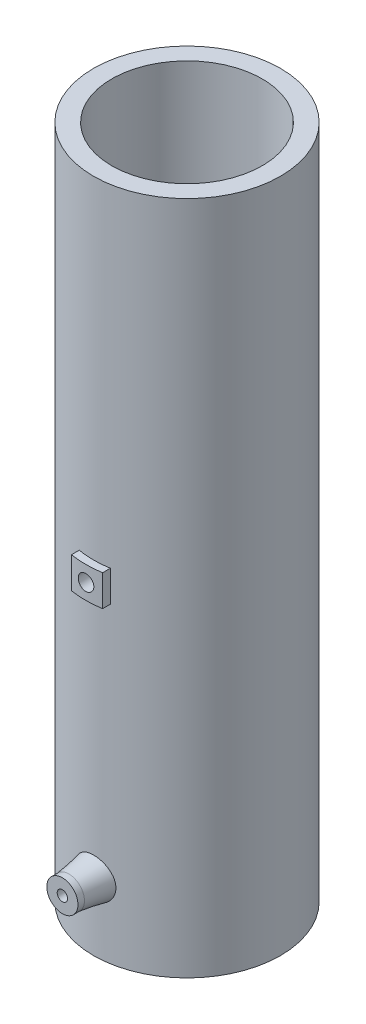
SolidWorks part; units mm, degrees
ref_plane "Front Plane" through (0, 0, 0) normal (0, 0, 1) x (1, 0, 0)
ref_plane "Top Plane" through (0, 0, 0) normal (0, 1, 0) x (1, 0, 0)
ref_plane "Right Plane" through (0, 0, 0) normal (1, 0, 0) x (0, 0, -1)
sketch "Sketch1" plane through (0, 0, 0) normal (0, 1, 0) x (1, 0, 0)
  circle A0 centre (0, 0) radius 18
  circle A1 centre (0, 0) radius 14.5
  dimension "D1" = 36
  dimension "D2" = 29
extrude "Boss-Extrude1" add sketch "Sketch1" along normal blind 130
fillet "Fillet1" radius 3 1 edges at (0, 0, 14.5)
ref_plane "Plane1" through (0, 0, 18) normal (0, 0, 1) x (1, 0, 0)
ref_plane "Plane2" through (0, 60, 0) normal (0, 1, 0) x (1, 0, 0)
sketch "Sketch3" plane through (0, 60, 0) normal (0, 1, 0) x (1, 0, 0)
  line L0 (-3, -19.2678) -> (-3, -17.7482)
  line L1 (-19.8, 0) -> (19.8, 0) construction
  line L2 (3, -19.2678) -> (3, -17.7482)
  line L3 (3, 19.2678) -> (3, 17.7482)
  line L4 (-3, 19.2678) -> (-3, 17.7482)
  arc A0 (-3, -17.7482) -> (3, -17.7482) centre (0, 0) ccw
  arc A1 (-3, -19.2678) -> (3, -19.2678) centre (0, 0) ccw
  arc A2 (-3, 19.2678) -> (3, 19.2678) centre (0, 0) cw
  arc A3 (-3, 17.7482) -> (3, 17.7482) centre (0, 0) cw
  dimension "D1" = 36
  dimension "D2" = 39
  dimension "D3" = 3
  dimension "D4" = 3
  dimension "D5" = 19.2678
extrude "Boss-Extrude2" add sketch "Sketch3" along normal blind 6
sketch "Sketch4" plane through (0, 0, 18) normal (0, 0, 1) x (1, 0, 0)
  line L0 (-3, 66) -> (-3, 60) construction
  line L1 (3, 66) -> (-3, 66) construction
  circle A0 centre (0, 63) radius 1.5
  dimension "D1" = 3
  dimension "D2" = 3
  dimension "D3" = 3
extrude "Cut-Extrude1" cut sketch "Sketch4" along normal blind 1.5 and the other way blind 1.5 contours A0
mirror "Mirror1" about plane through (0, 0, 0) normal (0, 0, 1) of "Cut-Extrude1"
sketch "Sketch5" plane through (0, 0, 18) normal (0, 0, 1) x (1, 0, 0)
  circle A0 centre (0, 13) radius 3
  circle A1 centre (0, 63) radius 1.5 construction
  dimension "D1" = 6
  dimension "D2" = 50
extrude "Boss-Extrude3" add sketch "Sketch5" along normal blind 6 and the other way blind 1 separate body
sketch "Sketch6" plane through (0, 0, 0) normal (1, 0, 0) x (0, 0, -1)
  line L0 (-11, 13) -> (-11, 19) construction
  line L1 (-24, 16) -> (-24, 10) construction
  line L2 (-17, 16) -> (-24, 16) construction
  line L3 (-22.7446, 16) -> (-22.7446, 13)
  line L4 (-22.7446, 13) -> (-16.5007, 13)
  line L5 (-16.5007, 17.1546) -> (-16.5007, 13)
  spline S0 degree 3 poles (-16.5007, 17.1546) (-18.5486, 16.6168) (-20.6299, 16.2319) (-22.7446, 16) knots 0.476119 0.476119 0.476119 0.476119 1 1 1 1
  dimension "D4" = 3
  dimension "D1" = 13
  dimension "D2" = 13
  dimension "D3" = 3
revolve "Revolve1" add sketch "Sketch6" angle 360 about L4
sketch "Sketch7" plane through (0, 0, 24) normal (0, 0, 1) x (1, 0, 0)
  circle A0 centre (0, 13) radius 1
  dimension "D1" = 2
extrude "Cut-Extrude2" cut sketch "Sketch7" against normal blind 6
ref_plane "Plane3" through (0, 70, 0) normal (0, 1, 0) x (1, 0, 0)
sketch "Sketch8" plane through (0, 70, 0) normal (0, 1, 0) x (1, 0, 0)
  circle A0 centre (0, 0) radius 14.5
  circle A1 centre (0, 0) radius 11.5
  dimension "D1" = 29
  dimension "D2" = 23
extrude "Boss-Extrude4" add sketch "Sketch8" along normal blind 10
fillet "Fillet2" radius 2 1 edges at (0, 80, 14.5)
